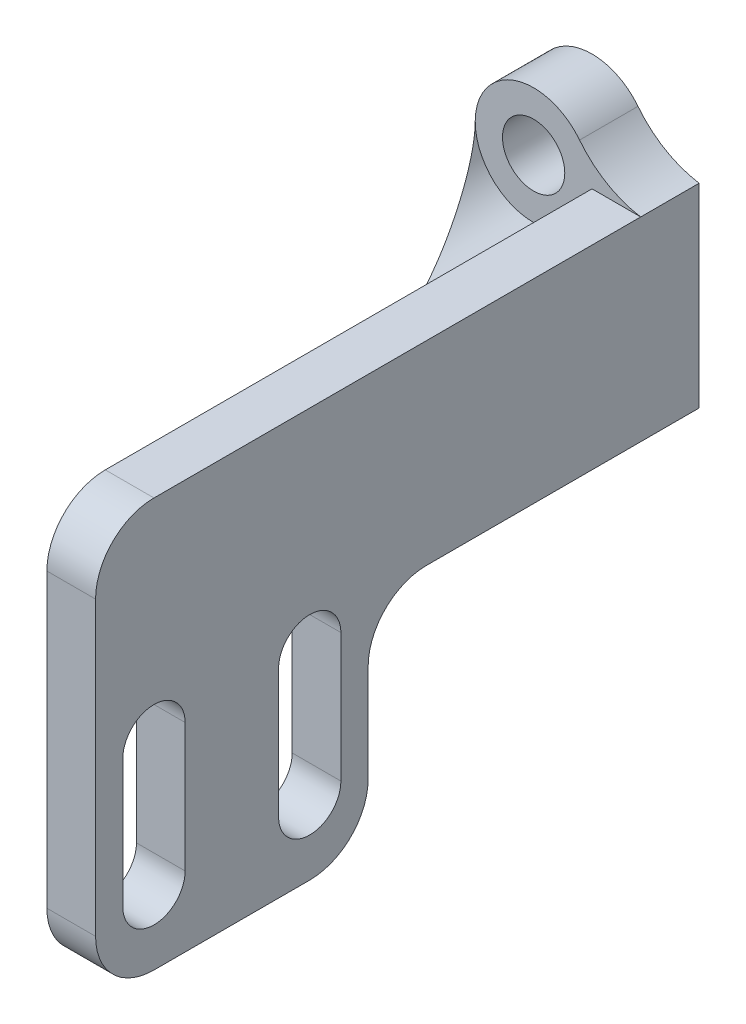
SolidWorks part; units mm, degrees
ref_plane "Front Plane" through (0, 0, 0) normal (0, 0, 1) x (1, 0, 0)
ref_plane "Top Plane" through (0, 0, 0) normal (0, 1, 0) x (1, 0, 0)
ref_plane "Right Plane" through (0, 0, 0) normal (1, 0, 0) x (0, 0, -1)
other "Configuration Table"
sketch "草图1" plane through (0, 0, 0) normal (0, 0, 1) x (1, 0, 0)
  line L0 (-3, -33.0103) -> (-3, -43.0103)
  line L1 (3, -33.0103) -> (3, -43.0103)
  line L3 (3, -33.0103) -> (5.5, -33.0103)
  line L4 (5.5, -33.0103) -> (5.5, -43.0103)
  line L5 (5.5, -43.0103) -> (3, -43.0103)
  circle A0 centre (0, -33.0103) radius 1.6
  circle A1 centre (0, -43.0103) radius 1.6
  circle A2 centre (0, -33.0103) radius 3
  circle A3 centre (0, -43.0103) radius 3
extrude "凸台-拉伸1" add sketch "草图1" along normal blind 3 contours A3 L1 A2 L0 | A2 A0 | A3 A1
sketch "草图2" plane through (0, 0, 3) normal (0, 0, 1) x (1, 0, 0)
  line L0 (0, -41.4103) -> (0, -34.6103) construction
  circle A0 centre (0, -43.0103) radius 1.6 construction
  circle A1 centre (0, -33.0103) radius 1.6 construction
sketch "草图3" plane through (0, 0, 3) normal (0, 0, 1) x (1, 0, 0)
  line L1 (5.5, -43.0103) -> (5.5, -33.0103)
  line L2 (5.5, -33.0103) -> (3, -33.0103)
  line L3 (3, -33.0103) -> (3, -43.0103)
  line L4 (3, -43.0103) -> (5.5, -43.0103)
extrude "凸台-拉伸2" add sketch "草图3" along normal blind 28
fillet "圆角1" radius 5 1 edges at (3, -43.0103, 1.5)
fillet "圆角2" radius 5 1 edges at (3, -33.0103, 1.5)
sketch "草图4" plane through (5.5, 0, 0) normal (1, 0, 0) x (0, 0, -1)
  line L1 (-31, -38.0103) -> (0, -38.0103) construction
  line L7 (-31, -43.0103) -> (-31, -33.0103) construction
  line L8 (0, -33.0103) -> (0, -43.0103) construction
  line L9 (-31, -43.0103) -> (-17, -43.0103)
  line L10 (-17, -54.0103) -> (-17, -43.0103)
  line L11 (-31, -54.0103) -> (-17, -54.0103)
  line L12 (-31, -43.0103) -> (-31, -54.0103)
extrude "凸台-拉伸3" add sketch "草图4" against normal up to surface (2.5 mm away) up to face at (3, -38.0103, 17)
sketch "草图5" plane through (5.5, 0, 0) normal (1, 0, 0) x (0, 0, -1)
  line L11 (0, -38.0103) -> (-31, -38.0103) construction
  line L12 (0, -33.0103) -> (0, -43.0103) construction
  line L13 (-31, -54.0103) -> (-31, -33.0103) construction
  line L14 (-28, -50.4028) -> (-28, -43.7974) construction
  line L15 (-26.4, -50.4028) -> (-26.4, -43.7974)
  line L16 (-29.6, -50.4028) -> (-29.6, -43.7974)
  line L17 (-20, -50.4028) -> (-20, -43.7974) construction
  line L18 (-21.6, -50.4028) -> (-21.6, -43.7974)
  line L19 (-18.4, -50.4028) -> (-18.4, -43.7974)
  line L20 (-24, -54.0103) -> (-24, -33.0103) construction
  line L21 (-28, -54.0103) -> (-28, -52.0103) construction
  line L22 (-24, -54.0103) -> (-28, -54.0103) construction
  arc A4 (-26.4, -50.4028) -> (-29.6, -50.4028) centre (-28, -50.4028) cw
  arc A5 (-29.6, -43.7974) -> (-26.4, -43.7974) centre (-28, -43.7974) cw
  arc A6 (-21.6, -50.4028) -> (-18.4, -50.4028) centre (-20, -50.4028) ccw
  arc A7 (-18.4, -43.7974) -> (-21.6, -43.7974) centre (-20, -43.7974) ccw
  point P30 (-28, -47.1001)
  point P37 (-20, -47.1001)
extrude "切除-拉伸1" cut sketch "草图5" against normal through all
sketch "草图6" plane through (0, -43.0103, 0) normal (0, -1, 0) x (1, 0, 0)
  line L0 (3, 14) -> (-3, 3)
  line L1 (-3, 3) -> (3, 3)
  line L2 (3, 3) -> (3, 14)
  line L3 (3, 17) -> (3, 3) construction
extrude "凸台-拉伸4" add sketch "草图6" against normal up to surface (10 mm away) up to face at (4.25, -33.0103, 17)
sketch "草图8" plane through (0, 0, 3) normal (0, 0, 1) x (1, 0, 0)
  line L0 (3, -43.0103) -> (-3, -43.0103) construction
  line L1 (3, -33.0103) -> (-3, -33.0103) construction
  circle A1 centre (0, -43.0103) radius 3
  circle A3 centre (0, -33.0103) radius 3
extrude "切除-拉伸2" cut sketch "草图8" along normal through all
fillet "圆角3" radius 3 4 edges at (4.25, -43.0103, 17) (4.25, -54.0103, 17) (4.25, -54.0103, 31) (4.25, -33.0103, 31)
